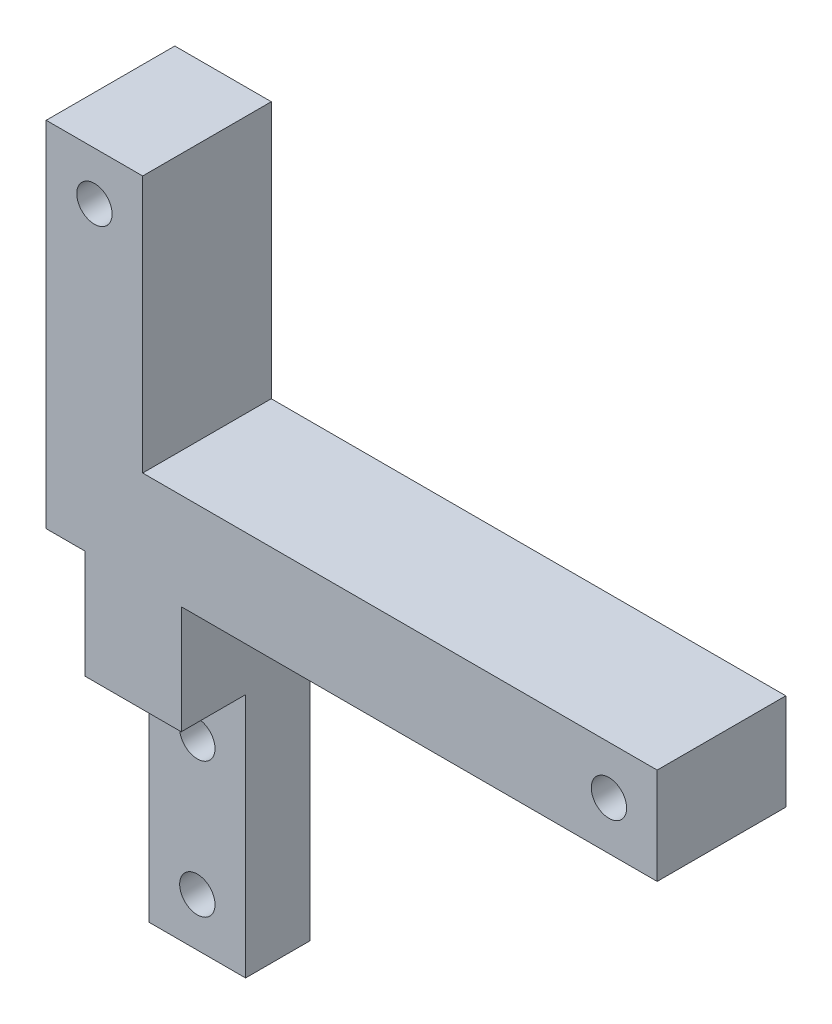
SolidWorks part; units mm, degrees
ref_plane "前视基准面" through (0, 0, 0) normal (0, 0, 1) x (1, 0, 0)
ref_plane "上视基准面" through (0, 0, 0) normal (0, 1, 0) x (1, 0, 0)
ref_plane "右视基准面" through (0, 0, 0) normal (1, 0, 0) x (0, 0, -1)
other "Configuration Table"
sketch "草图1" plane through (0, 0, 0) normal (0, 0, 1) x (1, 0, 0)
  line L0 (-5.3, -1.5) -> (9.5, -1.5)
  line L1 (-6.5, 1.5) -> (9.5, 1.5)
  line L4 (9.5, 1.5) -> (9.5, -1.5)
  line L5 (-9.5, 1.5) -> (9.5, -1.5) construction
  line L6 (-9.5, -1.5) -> (9.5, 1.5) construction
  line L8 (-9.5, 1.5) -> (-9.5, 9.5)
  line L9 (-9.5, 9.5) -> (-6.5, 9.5)
  line L11 (-6.5, 1.5) -> (-6.5, 9.5)
  line L12 (-9.5, 1.5) -> (-9.5, -1.5)
  line L13 (-8.3, -1.5) -> (-8.3, -12.5)
  line L14 (-8.3, -12.5) -> (-5.3, -12.5)
  line L15 (-5.3, -12.5) -> (-5.3, -1.5)
  line L16 (-9.5, -1.5) -> (-8.3, -1.5)
  circle A0 centre (8, 0) radius 0.55
  circle A1 centre (-8, 8) radius 0.55
  circle A2 centre (-6.8, -11) radius 0.55
  circle A3 centre (-6.8, -6.8) radius 0.55
  point P0 (0, 0)
  dimension "D3" = 1.1
  dimension "D8" = 1.1
  dimension "D15" = 1.1
  dimension "D16" = 1.1
  dimension "D1" = 19
  dimension "D2" = 3
  dimension "D4" = 1.5
  dimension "D5" = 1.5
  dimension "D6" = 11
  dimension "D7" = 3
  dimension "D9" = 1.5
  dimension "D10" = 1.5
  dimension "D14" = 19
  dimension "D17" = 4.2
  dimension "D18" = 1.5
extrude "凸台-拉伸1" add sketch "草图1" along normal blind 4
sketch "草图2" plane through (0, 0, 4) normal (0, 0, 1) x (1, 0, 0)
  line L0 (-8.3, -4.8687) -> (-5.3, -4.8687)
  line L10 (9.5, -1.5) -> (9.5, 1.5)
  line L11 (9.5, 1.5) -> (-6.5, 1.5)
  line L12 (-6.5, 1.5) -> (-6.5, 9.5)
  line L13 (-6.5, 9.5) -> (-9.5, 9.5)
  line L14 (-9.5, 9.5) -> (-9.5, -1.5)
  line L15 (-9.5, -1.5) -> (-8.3, -1.5)
  line L16 (-8.3, -1.5) -> (-8.3, -12.5)
  line L17 (-8.3, -12.5) -> (-5.3, -12.5)
  line L18 (-5.3, -12.5) -> (-5.3, -1.5)
  line L19 (-5.3, -1.5) -> (9.5, -1.5)
  line L26 (-8.3, -4.8687) -> (-8.3, -12.5)
  line L27 (-8.3, -12.5) -> (-5.3, -12.5)
  line L28 (-5.3, -12.5) -> (-5.3, -4.8687)
  circle A0 centre (-6.8, -11) radius 0.55 construction
  circle A1 centre (-6.8, -6.8) radius 0.55 construction
  circle A2 centre (-6.8, -11) radius 0.55
  circle A3 centre (-6.8, -6.8) radius 0.55
  dimension "D1" = 0
extrude "切除-拉伸1" cut sketch "草图2" against normal blind 2
